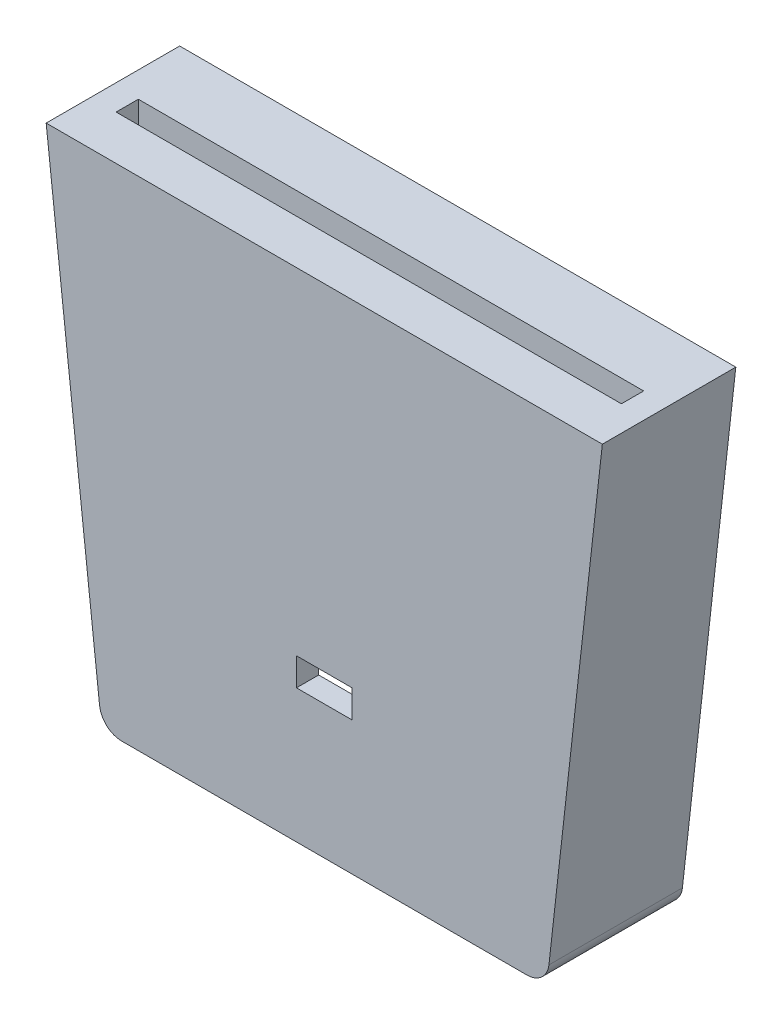
SolidWorks part; units mm, degrees
ref_plane "Front Plane" through (0, 0, 0) normal (0, 0, 1) x (1, 0, 0)
ref_plane "Top Plane" through (0, 0, 0) normal (0, 1, 0) x (1, 0, 0)
ref_plane "Right Plane" through (0, 0, 0) normal (1, 0, 0) x (0, 0, -1)
sketch "Sketch1" plane through (0, 0, 0) normal (0, 0, 1) x (1, 0, 0)
  line L0 (0, 56.7961) -> (0, -56.7961) construction
  line L1 (63.5, 56.7961) -> (-63.5, 56.7961)
  line L2 (-63.5, 56.7961) -> (-51.3049, -52.2806)
  line L3 (-46.2563, -56.7961) -> (46.2563, -56.7961)
  line L4 (63.5, 56.7961) -> (51.3049, -52.2806)
  line L5 (6.35, -19.9661) -> (-6.35, -19.9661)
  line L6 (-6.35, -19.9661) -> (-6.35, -26.3161)
  line L7 (-6.35, -26.3161) -> (6.35, -26.3161)
  line L8 (6.35, -19.9661) -> (6.35, -26.3161)
  arc A0 (-51.3049, -52.2806) -> (-46.2563, -56.7961) centre (-46.2563, -51.7161) ccw
  arc A1 (51.3049, -52.2806) -> (46.2563, -56.7961) centre (46.2563, -51.7161) cw
  point P10 (-50.8, -56.7961)
  point P16 (0, -26.3161)
  point P18 (0, -19.9661)
  dimension "D4" = 5.08
  dimension "D6" = 6.35
  dimension "D7" = 6.35
  dimension "D8" = 30.48
  dimension "D1" = 50.8
  dimension "D2" = 63.5
  dimension "D3" = 56.7961
  dimension "D5" = 109.0767
extrude "Boss-Extrude1" add sketch "Sketch1" against normal blind 5.08
sketch "Sketch2" plane through (0, 0, -5.08) normal (0, 0, 1) x (1, 0, 0)
  line L0 (0, 56.7961) -> (0, -56.7961) construction
  line L1 (63.5, 56.7961) -> (-63.5, 56.7961)
  line L2 (-63.5, 56.7961) -> (-51.3049, -52.2806)
  line L3 (-46.2563, -56.7961) -> (46.2563, -56.7961)
  line L4 (63.5, 56.7961) -> (51.3049, -52.2806)
  line L5 (6.35, -19.9661) -> (-6.35, -19.9661)
  line L6 (-6.35, -19.9661) -> (-6.35, -26.3161)
  line L7 (-6.35, -26.3161) -> (6.35, -26.3161)
  line L8 (6.35, -19.9661) -> (6.35, -26.3161)
  line L9 (-6.35, -19.9661) -> (-6.35, -26.3161) construction
  line L10 (6.35, -19.9661) -> (-6.35, -19.9661) construction
  line L11 (-57.8204, 51.7161) -> (57.8204, 51.7161)
  line L12 (57.8204, 51.7161) -> (46.7612, -47.2006)
  line L13 (41.7126, -51.7161) -> (-41.7126, -51.7161)
  line L14 (-57.8204, 51.7161) -> (-46.7612, -47.2006)
  arc A0 (-51.3049, -52.2806) -> (-46.2563, -56.7961) centre (-46.2563, -51.7161) ccw
  arc A1 (51.3049, -52.2806) -> (46.2563, -56.7961) centre (46.2563, -51.7161) cw
  arc A2 (46.7612, -47.2006) -> (41.7126, -51.7161) centre (41.7126, -46.6361) cw
  arc A3 (-46.7612, -47.2006) -> (-41.7126, -51.7161) centre (-41.7126, -46.6361) ccw
  point P10 (-50.8, -56.7961)
  point P16 (0, -26.3161)
  point P18 (0, -19.9661)
  point P30 (0, -51.7161)
  point P33 (0, 51.7161)
  arc M18 (51.3049, -52.2806) -> (46.2563, -56.7961) centre (46.2563, -51.7161) cw
  line M19 (46.2563, -56.7961) -> (-46.2563, -56.7961)
  arc M20 (-46.2563, -56.7961) -> (-51.3049, -52.2806) centre (-46.2563, -51.7161) cw
  line M21 (-51.3049, -52.2806) -> (-63.5, 56.7961)
  line M22 (-63.5, 56.7961) -> (63.5, 56.7961)
  line M23 (63.5, 56.7961) -> (51.3049, -52.2806)
  dimension "D4" = 5.08
  dimension "D6" = 6.35
  dimension "D7" = 6.35
  dimension "D8" = 30.48
  dimension "D9" = 0
  dimension "D10" = 5.08
  dimension "D1" = 50.8
  dimension "D2" = 63.5
  dimension "D3" = 5.08
  dimension "D5" = 109.0767
extrude "Boss-Extrude2" add sketch "Sketch2" against normal blind 25.4 contours L0 L1 L13 A2 L12 L11 M23 M18 M19 | L0 L11 L14 A3 L13 L3 M22 M20 M21 region at (31.75, 55.4948, -5.08) region at (-1.3014, 54.2561, -5.08)
sketch "Sketch4" plane through (0, 56.7961, -56.7961) normal (0, -1, 0) x (1, 0, 0)
  line L0 (57.6928, 41.5561) -> (57.6928, 46.6361)
  line L1 (57.6928, 41.5561) -> (-57.6928, 41.5561)
  line L2 (57.6928, 46.6361) -> (-57.6928, 46.6361)
  line L3 (-57.6928, 41.5561) -> (-57.6928, 46.6361)
  line L4 (63.5, 56.7961) -> (-63.5, 56.7961) construction
  dimension "D1" = 115.3856
  dimension "D2" = 10.16
  dimension "D4" = 5.08
extrude "Cut-Extrude1" cut sketch "Sketch4" along normal blind 5.08
sketch "Sketch6" plane through (0, 0, -30.48) normal (0, 0, 1) x (1, 0, 0)
  line L0 (0, 50.5747) -> (0, -51.7161) construction
  line L3 (-52.9958, 8.564) -> (-33.9458, 8.564)
  line L5 (-33.9458, 8.564) -> (-33.9458, -4.136)
  line L6 (-33.9458, -4.136) -> (-51.5759, -4.136)
  line L8 (33.9458, -4.136) -> (51.5759, -4.136)
  line L9 (33.9458, 8.564) -> (33.9458, -4.136)
  line L10 (52.9958, 8.564) -> (33.9458, 8.564)
  line L11 (-51.5759, -4.136) -> (-52.9958, 8.564)
  line L12 (52.9958, 8.564) -> (51.5759, -4.136)
  line L13 (-57.8204, 51.7161) -> (57.8204, 51.7161) construction
  dimension "D1" = 19.05
  dimension "D2" = 12.7
  dimension "D3" = 33.9458
  dimension "D4" = 4.8246
  dimension "D5" = 6.2445
  dimension "D6" = 43.1521
extrude "Boss-Extrude3" add sketch "Sketch6" along normal blind 2.54
sketch "Sketch7" plane through (0, 0, -30.48) normal (0, 0, 1) x (1, 0, 0)
  line L0 (-43.4708, 8.564) -> (-42.7609, -4.136) construction
  line L1 (-63.5, 56.7961) -> (63.5, 56.7961) construction
  line L2 (-51.5759, -4.136) -> (-33.9458, -4.136) construction
  line L3 (0, 56.7961) -> (0, -51.7161) construction
  line L4 (-33.9458, 8.564) -> (-52.9958, 8.564) construction
  line L6 (-33.9458, -4.136) -> (-33.9458, 8.564) construction
  line L7 (-57.8204, 51.7161) -> (57.8204, 51.7161) construction
  circle A0 centre (-43.1159, 2.214) radius 1.905
  circle A2 centre (43.1159, 2.214) radius 1.905
  dimension "D1" = 3.81
extrude "Cut-Extrude2" cut sketch "Sketch7" along normal blind 2.54
